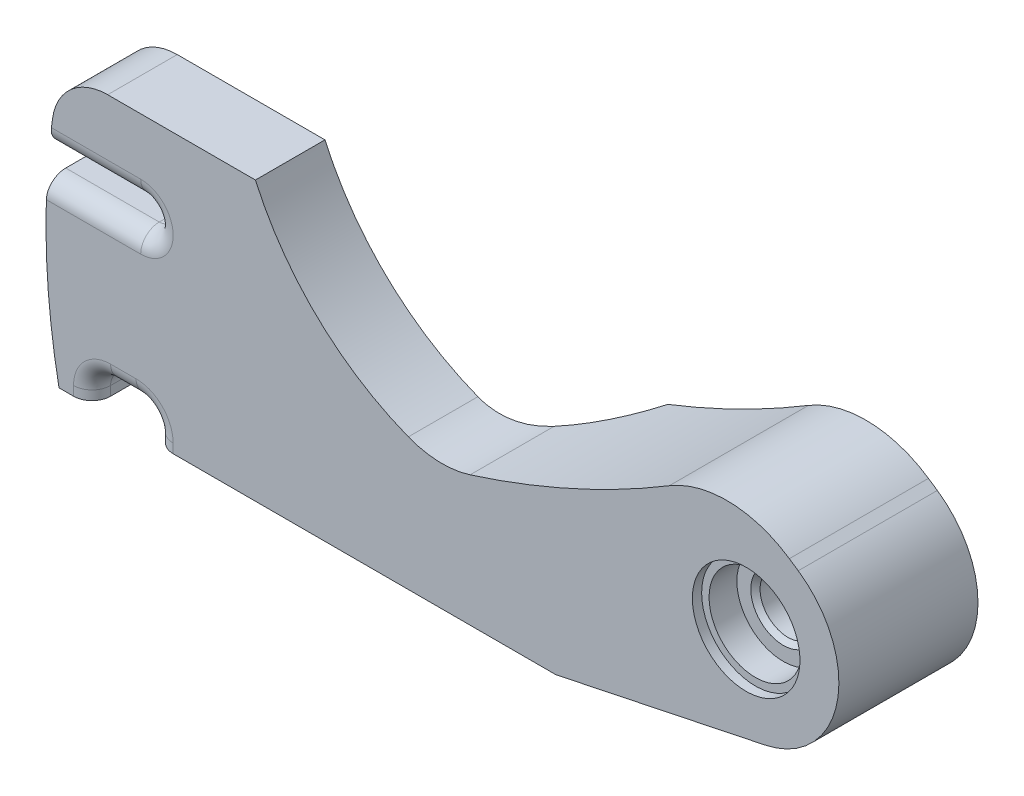
SolidWorks part; units mm, degrees
ref_plane "Front Plane" through (0, 0, 0) normal (0, 0, 1) x (1, 0, 0)
ref_plane "Top Plane" through (0, 0, 0) normal (0, 1, 0) x (1, 0, 0)
ref_plane "Right Plane" through (0, 0, 0) normal (1, 0, 0) x (0, 0, -1)
sketch "Sketch1" plane through (0, 0, 0) normal (0, 0, 1) x (1, 0, 0)
  line L0 (-5.0316, 15.5) -> (5.6154, 8.2745)
  line L1 (-77, 15.5) -> (-5.0316, 15.5)
  line L2 (-77, 15.5) -> (-77, -14.5)
  line L3 (-77, -14.5) -> (-20.5223, -14.5)
  line L5 (-20.5223, -14.5) -> (2.0436, -9.789)
  circle A0 centre (0, 0) radius 3
  arc A1 (2.0436, -9.789) -> (5.6154, 8.2745) centre (0, 0) ccw
  dimension "D1" = 6
  dimension "D2" = 10
  dimension "D3" = 77
  dimension "D4" = 30
  dimension "D5" = 15.5
extrude "Boss-Extrude1" add sketch "Sketch1" along normal mid plane 26
sketch "Sketch2" plane through (0, 0, 13) normal (0, 0, 1) x (1, 0, 0)
  circle A0 centre (0, 0) radius 21.5991
extrude "Cut-Extrude1" cut sketch "Sketch2" against normal blind 5.5
fillet "Fillet1" radius 10 1 edges at (-21.5645, 1.222, 7.5)
mirror "Mirror1" about plane through (0, 0, 0) normal (0, 0, 1) of "Fillet1", "Cut-Extrude1"
sketch "Sketch5" plane through (0, 0, 0) normal (0, 0, 1) x (1, 0, 0)
  circle A0 centre (0, 0) radius 75.5
  circle A1 centre (0, 0) radius 126.6666
  dimension "D1" = 151
extrude "Cut-Extrude3" cut sketch "Sketch5" against normal through all both and the other way through all
sketch "Sketch7" plane through (0, 0, 0) normal (0, 1, 0) x (1, 0, 0)
  line L0 (10, 0) -> (-5.0316, 0) construction
  line L1 (10, -7.5) -> (10, 7.5) construction
  line L2 (-5.0316, -8.1811) -> (-5.0316, 8.1811) construction
  line L3 (0, 0) -> (0, -11.8109) construction
  line L4 (5.6154, -7.5) -> (-0.8205, -7.5) construction
  line L5 (0, -7.5) -> (5.8, -7.5)
  line L7 (5, -6.5) -> (5.8, -6.5)
  line L8 (5.8, -7.5) -> (5.8, -6.5)
  line L9 (0, -3.5) -> (0, -7.5)
  line L11 (5, -6.5) -> (5, -3.5)
  line L12 (5, -3.5) -> (0, -3.5)
  line L14 (5, 3.5) -> (0, 3.5)
  line L15 (5, 6.5) -> (5, 3.5)
  line L16 (0, 3.5) -> (0, 7.5)
  line L17 (5.8, 7.5) -> (5.8, 6.5)
  line L18 (5, 6.5) -> (5.8, 6.5)
  line L19 (0, 7.5) -> (5.8, 7.5)
  dimension "D1" = 4
  dimension "D2" = 5
  dimension "D3" = 5.8
  dimension "D4" = 1
revolve "Cut-Revolve1" cut sketch "Sketch7" angle 360 about L3
sketch "Sketch4" plane through (0, 0, 0) normal (0, 0, 1) x (1, 0, 0)
  line L0 (-54.9514, 21.9352) -> (-30.5446, 32.0637)
  line L1 (-30.5446, 32.0637) -> (0.9831, 15.5998)
  line L2 (-32.7874, 125.3266) -> (-32.7874, 76.5609) construction
  line L5 (-54.0551, -0.9246) -> (-5.4084, -0.9246) construction
  arc A0 (-36.4254, -0.2394) -> (-29.7662, -0.4573) centre (-32.7874, 9.0754) ccw
  arc A1 (-29.7662, -0.4573) -> (0.9831, 15.5998) centre (-59.9784, 94.8696) ccw
  arc A2 (-54.9514, 21.9352) -> (-36.4254, -0.2394) centre (-25.5114, 27.7049) ccw
  point P9 (-14.1668, 5.9804)
  dimension "D1" = 20
  dimension "D2" = 100
  dimension "D3" = 30
  dimension "D4" = 0.9246
extrude "Cut-Extrude2" cut sketch "Sketch4" against normal through all both and the other way through all
ref_plane "Plane1" through (0, 0, 4.5) normal (0, 0, 1) x (1, 0, 0)
sketch "Sketch6" plane through (0, 0, 4.5) normal (0, 0, 1) x (1, 0, 0)
  line L2 (-30.5446, 32.0637) -> (-54.9514, 21.9352)
  line L3 (0.9831, 15.5998) -> (-30.5446, 32.0637)
  arc A0 (-49.5541, 22.993) -> (-34.4245, 4.8837) centre (-25.5114, 27.7049) ccw
  arc A1 (-34.4245, 4.8837) -> (-31.4278, 4.7857) centre (-32.7874, 9.0754) ccw
  arc A2 (-31.4278, 4.7857) -> (-2.3697, 19.9597) centre (-59.9784, 94.8696) ccw
  arc A3 (-29.7662, -0.4573) -> (0.9831, 15.5998) centre (-59.9784, 94.8696) ccw
  arc A4 (-36.4254, -0.2394) -> (-29.7662, -0.4573) centre (-32.7874, 9.0754) ccw
  arc A5 (-54.9514, 21.9352) -> (-36.4254, -0.2394) centre (-25.5114, 27.7049) ccw
  arc A6 (-29.7662, -0.4573) -> (0.9831, 15.5998) centre (-59.9784, 94.8696) ccw construction
  arc A7 (-36.4254, -0.2394) -> (-29.7662, -0.4573) centre (-32.7874, 9.0754) ccw construction
  arc A8 (-54.9514, 21.9352) -> (-36.4254, -0.2394) centre (-25.5114, 27.7049) ccw construction
  dimension "D1" = 0
  dimension "D2" = 5.5
fillet "Fillet2" radius 12 1 edges at (-1.964, 13.4182, 0)
fillet "Fillet3" radius 6 1 edges at (-73.8918, 15.5, 0)
chamfer "Chamfer1" distance 0.5 angle 45 2 edges at (-3, 0, -3.5) (3, 0, 3.5)
sketch "Sketch8" plane through (0, 0, -13) normal (0, 0, -1) x (-1, 0, 0)
  line L0 (63.7868, 69.075) -> (63.7868, -26.1176) construction
  line L1 (74.0945, -14.5) -> (20.5223, -14.5) construction
  line L2 (63.7868, -14.5) -> (70.5305, -14.5)
  line L3 (63.7868, -14.5) -> (63.7868, -11.5)
  line L4 (63.7868, -11.5) -> (70.5305, -11.5)
  line L5 (70.5305, -14.5) -> (70.5305, -11.5)
  line L7 (63.7868, 4.3899) -> (77.7571, 4.3899)
  line L8 (63.7868, 4.3899) -> (63.7868, 7.3899)
  line L9 (63.7868, 7.3899) -> (77.7571, 7.3899)
  line L10 (77.7571, 4.3899) -> (77.7571, 7.3899)
  dimension "D1" = 3
extrude "Cut-Extrude4" cut sketch "Sketch8" against normal through all
fillet "Fillet4" radius 3 6 edges at (-69.5795, 4.3899, 13) (-69.4621, 7.3899, 13) (-67.1586, -11.5, 13) (-67.1586, -11.5, -13) (-69.4621, 7.3899, -13) (-69.5795, 4.3899, -13)
sketch "Sketch9" plane through (0, 15.5, 0) normal (0, 1, 0) x (1, 0, 0)
  line L1 (-84.9575, 21.1863) -> (10, 21.1863)
  line L2 (-84.9575, 21.1863) -> (-84.9575, 7.5)
  line L3 (-84.9575, 7.5) -> (10, 7.5)
  line L4 (10, 21.1863) -> (10, 7.5)
  line L5 (10, -7.5) -> (-85.7047, -7.5)
  line L6 (10, -7.5) -> (10, -21.3662)
  line L7 (10, -21.3662) -> (-85.7047, -21.3662)
  line L8 (-85.7047, -7.5) -> (-85.7047, -21.3662)
extrude "Cut-Extrude5" cut sketch "Sketch9" against normal through all both and the other way through all
sketch "Sketch10" plane through (0, 0, 0) normal (0, 1, 0) x (1, 0, 0)
  line L0 (0, 0) -> (-23.4341, 0) construction
  line L10 (-23.4341, 0) -> (-80.6322, 0)
  line L11 (-23.4341, 0) -> (-23.4341, 10.1088)
  line L12 (-23.4341, 10.1088) -> (-80.6322, 10.1088)
  line L13 (-80.6322, 0) -> (-80.6322, 10.1088)
revolve "Cut-Revolve2" cut sketch "Sketch10" angle 360 about L13
fillet "Fillet7" radius 15 1 edges at (-23.7965, -6.4285, 0)
fillet "Fillet8" 2 edges at (-63.7868, 4.3899, 3.75) (-63.7868, 7.3899, 3.75) type full round first side face at (-69.5795, 4.3899, 3.75) second side face at (-69.4621, 7.3899, 3.75) middle face at (-63.7868, 5.8899, 3.75)
fillet "Fillet9" radius 2 2 edges at (-70.5305, -11.5, 3.75) (-63.7868, -11.5, 3.75)
fillet "Fillet10" radius 2 16 edges at (-70.5305, -14, 7.5) (-69.9447, -12.0858, 7.5) (-67.1586, -11.5, 7.5) (-63.7868, -14, 7.5) (-70.3295, 4.3899, 7.5) (-70.2121, 7.3899, 7.5) (-70.2121, 7.3899, 0) (-70.3295, 4.3899, 0) (-70.5305, -14, 0) (-69.9447, -12.0858, 0) (-63.7868, -14, 0) (-64.3725, -12.0858, 0) (-64.3725, -12.0858, 7.5) (-63.7868, 5.8899, 7.5) (-63.7868, 5.8899, 0) (-67.1586, -11.5, 0)
